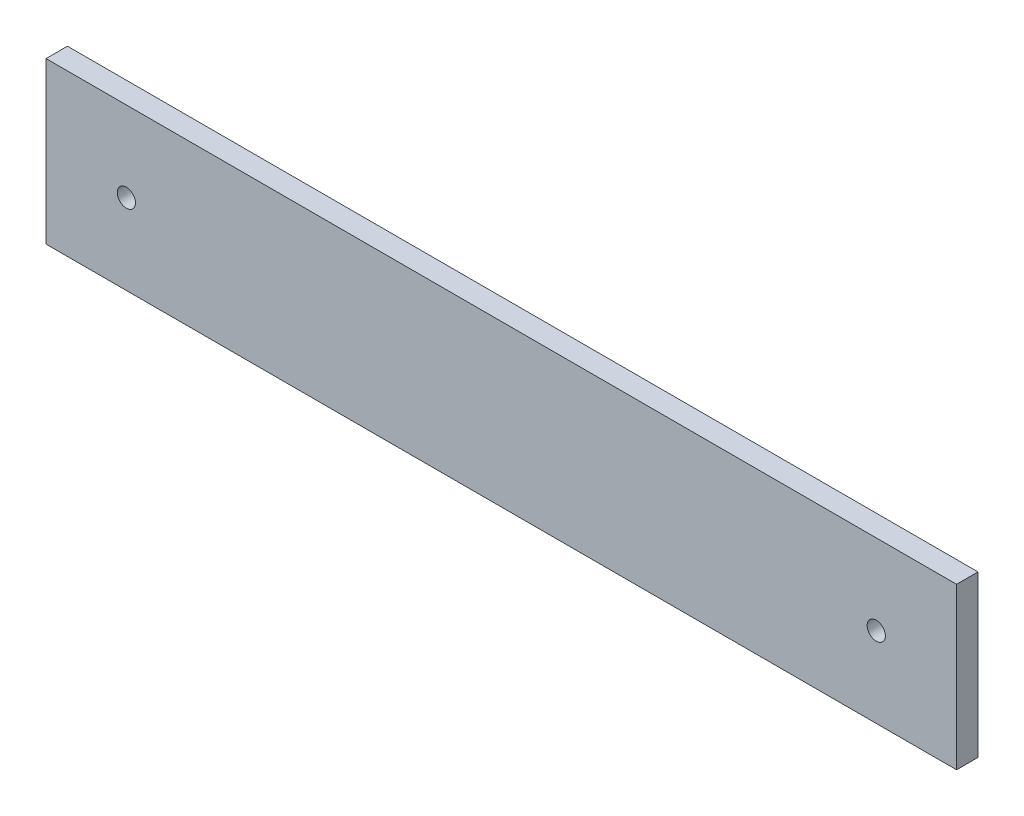
SolidWorks part; units mm, degrees
ref_plane "前视基准面" through (0, 0, 0) normal (0, 0, 1) x (1, 0, 0)
ref_plane "上视基准面" through (0, 0, 0) normal (0, 1, 0) x (1, 0, 0)
ref_plane "右视基准面" through (0, 0, 0) normal (1, 0, 0) x (0, 0, -1)
other "Configuration Table"
sketch "草图1" plane through (0, 0, 0) normal (0, 0, 1) x (1, 0, 0)
  line L1 (-15, -15) -> (155, -15)
  line L2 (-15, -15) -> (-15, 15)
  line L3 (-15, 15) -> (155, 15)
  line L4 (155, -15) -> (155, 15)
  line L5 (-15, -15) -> (155, 15) construction
  line L6 (-15, 15) -> (155, -15) construction
  circle A0 centre (0, 0) radius 1.7
  circle A1 centre (140, 0) radius 1.7
extrude "凸台-拉伸1" add sketch "草图1" along normal mid plane 4
